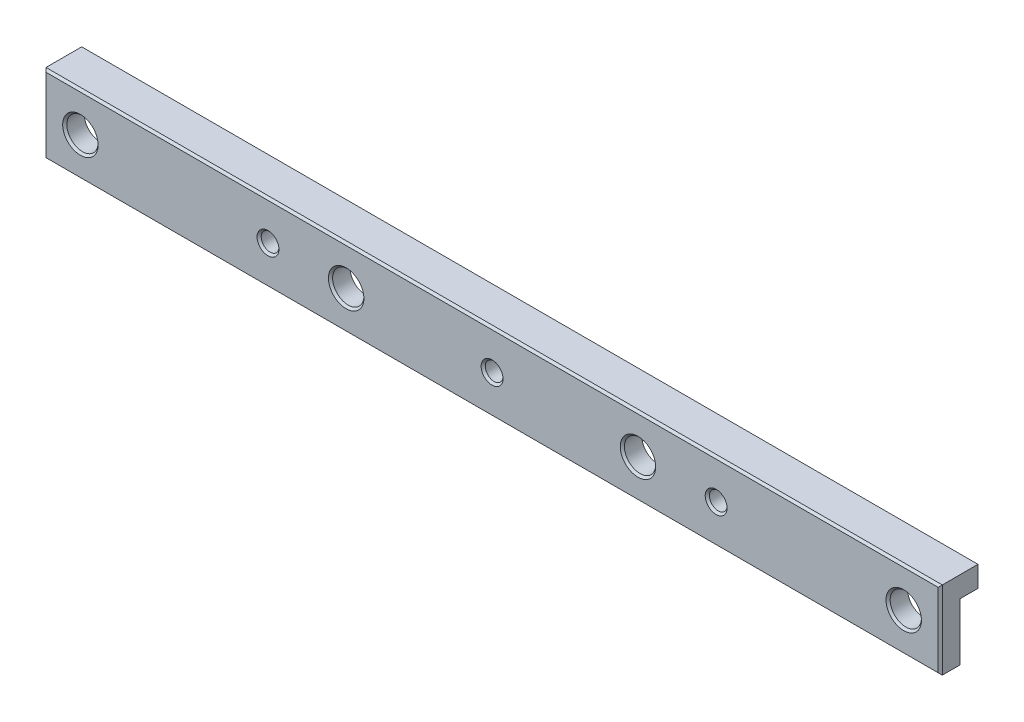
SolidWorks part; units mm, degrees
ref_plane "Front Plane" through (0, 0, 0) normal (0, 0, 1) x (1, 0, 0)
ref_plane "Top Plane" through (0, 0, 0) normal (0, 1, 0) x (1, 0, 0)
ref_plane "Right Plane" through (0, 0, 0) normal (1, 0, 0) x (0, 0, -1)
sketch "Sketch1" plane through (0, 0, 0) normal (0, 0, 1) x (1, 0, 0)
  line L0 (0, 7.5) -> (0, 0) construction
  line L1 (86, 7.5) -> (-86, 7.5)
  line L2 (86, 7.5) -> (86, 3.5)
  line L3 (86, -7.5) -> (-86, -7.5)
  line L4 (-86, 7.5) -> (-86, 3.5)
  line L5 (86, 3.5) -> (-86, 3.5)
  line L6 (-86, 3.5) -> (-86, -7.5)
  line L7 (86, 3.5) -> (86, -7.5)
  line L8 (0, 0) -> (0, -7.5) construction
  dimension "D1" = 172
  dimension "D2" = 7.5
  dimension "D3" = 4
extrude "Boss-Extrude1" add sketch "Sketch1" against normal blind 7.25 contours L7 L5 L6 L3 | L1 L0 L5 L2 | L0 L1 L4 L5 region at (0, 5.5, 0) region at (0, -2, 0)
extrude "Cut-Extrude1" cut sketch "Sketch1<6>" along normal blind 3.5 from surface contours L7 L5 L6 L3 region at (0, -2, 0) starting at face at (0, 0, -7.25)
sketch "Sketch1<6>" plane through (0, 0, 0) normal (0, 0, 1) x (1, 0, 0) same geometry as "Sketch1"
sketch "Sketch2" plane through (0, 0, 0) normal (0, 0, 1) x (1, 0, 0)
  line L0 (79, 0) -> (0, 0) construction
  line L1 (-86, 3.5) -> (-86, -7.5) construction
  line L2 (0, 0) -> (-79, 0) construction
  line L4 (-86, 0) -> (-43, 0) construction
  line L5 (-43, 0) -> (0, 0) construction
  line L6 (0, 0) -> (43, 0) construction
  line L7 (43, 0) -> (86, 0) construction
  circle A1 centre (-43, 0) radius 1.7
  circle A2 centre (0, 0) radius 1.7
  circle A3 centre (43, 0) radius 1.7
  circle A4 centre (-79, 0) radius 3
  circle A7 centre (79, 0) radius 3
  circle A10 centre (-28, 0) radius 3
  circle A11 centre (28, 0) radius 3
  dimension "D2" = 6
  dimension "D4" = 28
  dimension "D3" = 3.4
  dimension "D1" = 7
  dimension "D5" = 79
  dimension "D6" = 79
  dimension "D7" = 28
extrude "Cut-Extrude2" cut sketch "Sketch2" against normal through all both and the other way through all
chamfer "Chamfer1" distance 0.4 angle 45 11 edges at (0, -7.5, 0) (-86, 0, 0) (0, 7.5, 0) (86, 0, 0) (1.7, 0, 0) (31, 0, 0) (-25, 0, 0) (-41.3, 0, 0) (44.7, 0, 0) (-76, 0, 0) (82, 0, 0)
